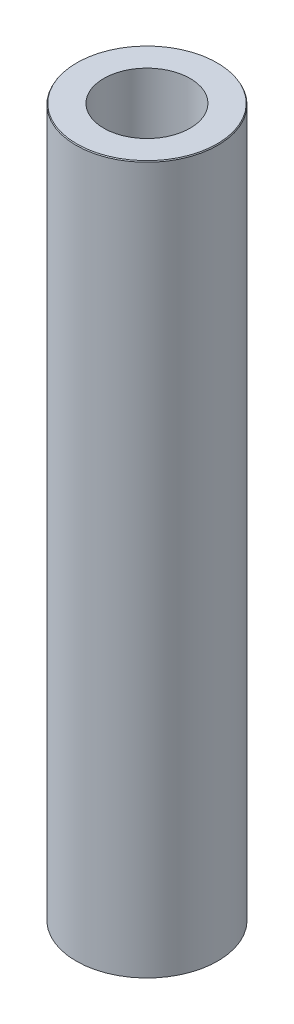
SolidWorks part; units mm, degrees
ref_plane "Front Plane" through (0, 0, 0) normal (0, 0, 1) x (1, 0, 0)
ref_plane "Top Plane" through (0, 0, 0) normal (0, 1, 0) x (1, 0, 0)
ref_plane "Right Plane" through (0, 0, 0) normal (1, 0, 0) x (0, 0, -1)
sketch "Sketch1" plane through (0, 0, 0) normal (0, 1, 0) x (1, 0, 0)
  circle A0 centre (0, 0) radius 60
  dimension "SHAFT_OD" = 120
extrude "Boss-Extrude1" add sketch "Sketch1" along normal blind 600
sketch "Sketch2" plane through (0, 0, 0) normal (0, 1, 0) x (1, 0, 0)
  circle A0 centre (0, 0) radius 36.5787
  dimension "BORE_D" = 73.1575
extrude "Cut-Extrude1" cut sketch "Sketch2" along normal through all
chamfer "Chamfer1" distance 0.861 angle 30 2 edges at (0, 600, 60) (0, 0, 60) first distance on face at (0, 600, 60) first distance on face at (0, 0, 36.5787)
